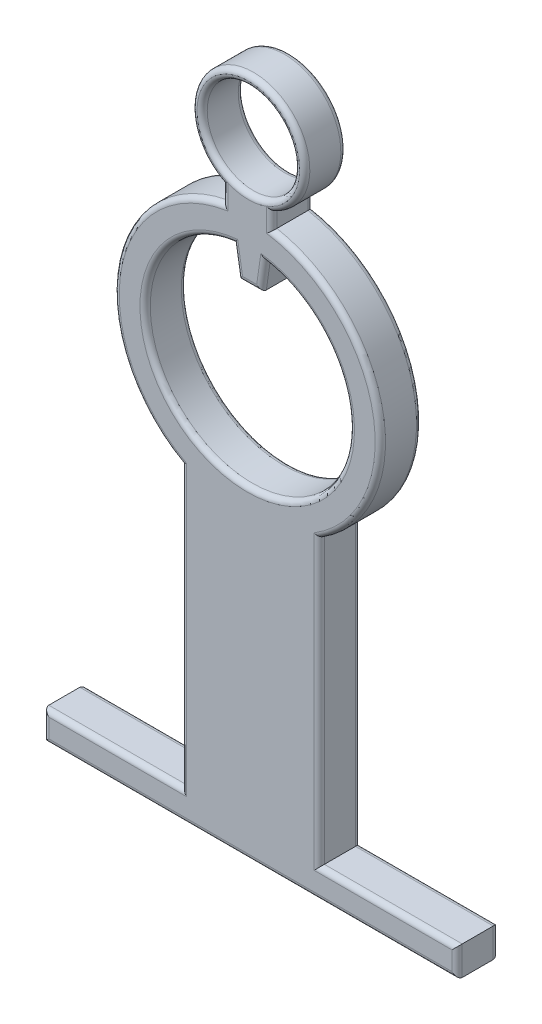
SolidWorks part; units mm, degrees
ref_plane "Front Plane" through (0, 0, 0) normal (0, 0, 1) x (1, 0, 0)
ref_plane "Top Plane" through (0, 0, 0) normal (0, 1, 0) x (1, 0, 0)
ref_plane "Right Plane" through (0, 0, 0) normal (1, 0, 0) x (0, 0, -1)
sketch "Sketch3" plane through (0, 0, 0) normal (0, 0, 1) x (1, 0, 0)
  line L0 (1.4933, 10.0912) -> (1.0571, 7.0335)
  line L5 (-2.671, 14.6921) -> (2.0797, 14.6921)
  line L6 (-2.671, 14.6921) -> (-2.671, 10.2605)
  line L7 (-2.671, 10.2605) -> (2.0797, 10.2605)
  line L8 (2.0797, 14.6921) -> (2.0797, 10.2605)
  line L11 (1.0571, 7.0335) -> (-1.1676, 7.0134)
  line L13 (-1.1676, 7.0134) -> (-1.6714, 10.0655)
  line L14 (-1.6714, 10.0655) -> (1.4933, 10.0912)
  circle A0 centre (-0.1875, 19.204) radius 4.4759
  circle A1 centre (-0.1875, 19.204) radius 5.4512
  circle A2 centre (-0.2956, 0.0477) radius 9.8777
  circle A3 centre (-0.2956, 0.0477) radius 12.8777
extrude "Boss-Extrude1" add sketch "Sketch3" along normal blind 4 contours L6 L7 L8 L5
extrude "Boss-Extrude2" add sketch "Sketch3<3>" along normal blind 4 contours L8 A1 L6 L5 A0 region at (-2.8217, 14.5218, 0)
sketch "Sketch3<3>" plane through (0, 0, 0) normal (0, 0, 1) x (1, 0, 0) same geometry as "Sketch3"
extrude "Boss-Extrude3" add sketch "Sketch3<4>" along normal blind 4 contours L6 A3 L8 L7 A2 | L14 L0 L11 L13 region at (-3.0337, 11.4824, 0)
sketch "Sketch3<4>" plane through (0, 0, 0) normal (0, 0, 1) x (1, 0, 0) same geometry as "Sketch3"
sketch "Sketch4" plane through (0, 0, 0) normal (0, 0, 1) x (1, 0, 0)
  line L0 (-6.6612, -9.8684) -> (6.6722, -9.8684)
  line L1 (6.6722, -9.8684) -> (6.6722, -38.28)
  line L2 (6.6722, -38.28) -> (20.0055, -38.28)
  line L3 (20.0055, -38.28) -> (20.0055, -41.096)
  line L4 (20.0055, -41.096) -> (-19.9945, -41.096)
  line L5 (-19.9945, -41.096) -> (-19.9945, -38.28)
  line L6 (-19.9945, -38.28) -> (-6.6612, -38.28)
  line L7 (-6.6612, -38.28) -> (-6.6612, -9.8684)
  line L8 (2.0797, 14.2467) -> (2.0797, 12.7044) construction
  circle A0 centre (-0.1875, 19.204) radius 4.4759 construction
  point P4 (5, -0.0426)
  dimension "D2" = 60.3
  dimension "D1" = 40
  dimension "D3" = 2.8159
extrude "Boss-Extrude5" add sketch "Sketch4" along normal blind 4
fillet "Fillet2" radius 0.5 34 edges at (-1.4004, 8.4239, 0) (-0.0553, 7.0235, 0) (1.2523, 8.4019, 0) (-0.5009, -9.8278, 0) (4.2884, 19.204, 0) (2.0797, 13.4756, 0) (-0.0673, 24.6539, 0) (-2.671, 13.5279, 0) (-12.9968, 2.1726, 0) (-6.6612, -24.7134, 0) (-13.3278, -38.28, 0) (-19.9945, -39.688, 0) (0.0055, -41.096, 0) (20.0055, -39.688, 0) (13.3388, -38.28, 0) (6.6722, -24.531, 0) (12.3427, 2.519, 0) (4.2884, 19.204, 4) (1.2523, 8.4019, 4) (-0.0553, 7.0235, 4) (-1.4004, 8.4239, 4) (-0.5009, -9.8278, 4) (13.3388, -38.28, 4) (20.0055, -39.688, 4) (0.0055, -41.096, 4) (-19.9945, -39.688, 4) (-13.3278, -38.28, 4) (-6.6612, -24.7134, 4) (-12.9968, 2.1726, 4) (-2.671, 13.5279, 4) (-0.0673, 24.6539, 4) (2.0797, 13.4756, 4) (12.3427, 2.519, 4) (6.6722, -24.531, 4)
